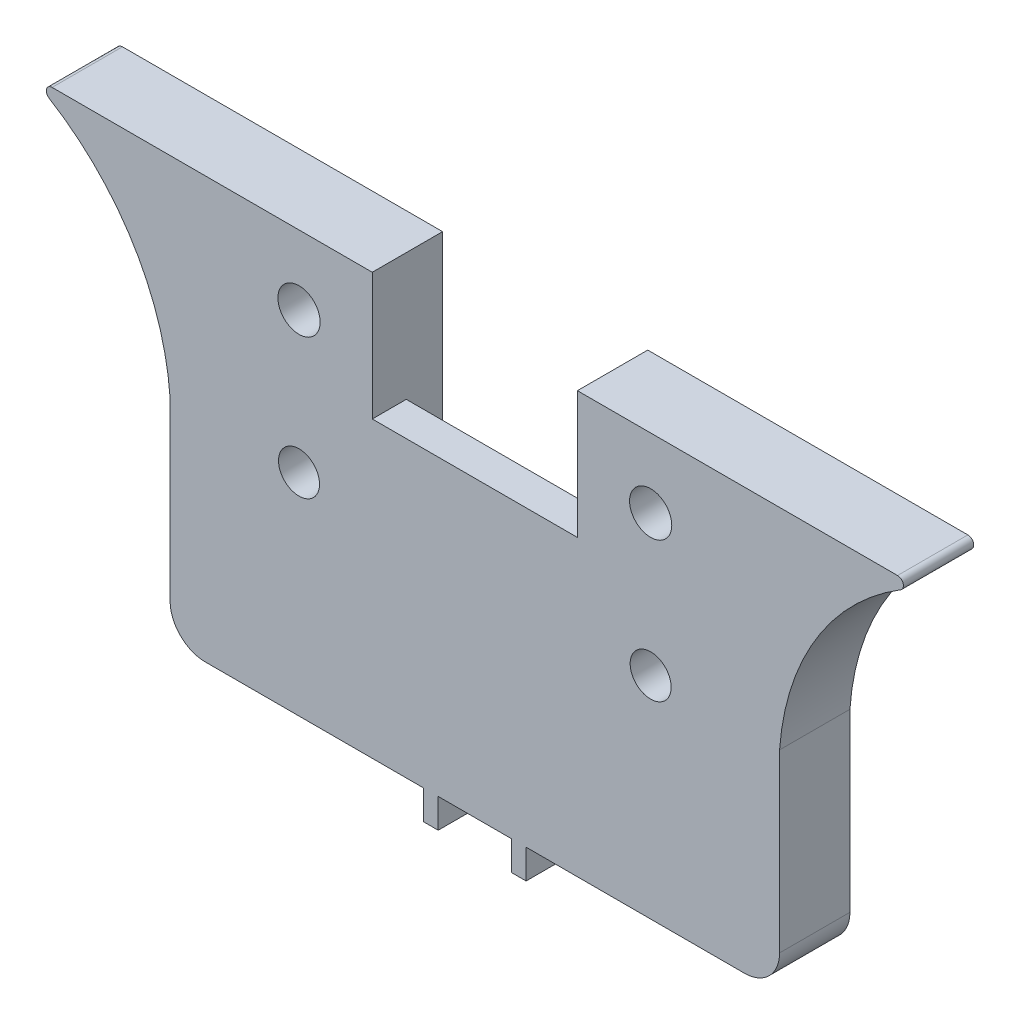
SolidWorks part; units mm, degrees
ref_plane "Front Plane" through (0, 0, 0) normal (0, 0, 1) x (1, 0, 0)
ref_plane "Top Plane" through (0, 0, 0) normal (0, 1, 0) x (1, 0, 0)
ref_plane "Right Plane" through (0, 0, 0) normal (1, 0, 0) x (0, 0, -1)
sketch "Sketch2" plane through (0, 0, 0) normal (0, 0, 1) x (1, 0, 0)
  line L0 (0, -33.2846) -> (0, 67.9981) construction
  line L12 (45.8007, 37.8996) -> (-45.8007, 37.8996)
  line L13 (-33.02, 15.1445) -> (-33.02, -3.9055)
  line L14 (-29.21, -7.7155) -> (29.21, -7.7155)
  line L15 (33.02, 15.1445) -> (33.02, -3.9055)
  circle A4 centre (-19.05, 15.1445) radius 2.2225
  circle A12 centre (19.05, 15.1445) radius 2.2225
  arc A13 (-33.02, 15.1445) -> (-46.1321, 36.723) centre (-60.5269, 13.203) ccw
  arc A14 (33.02, 15.1445) -> (46.1321, 36.723) centre (60.5269, 13.203) cw
  arc A15 (33.02, -3.9055) -> (29.21, -7.7155) centre (29.21, -3.9055) cw
  arc A16 (-33.02, -3.9055) -> (-29.21, -7.7155) centre (-29.21, -3.9055) ccw
  arc A17 (46.1321, 36.723) -> (45.8007, 37.8996) centre (45.8007, 37.2646) ccw
  arc A18 (-45.8007, 37.8996) -> (-46.1321, 36.723) centre (-45.8007, 37.2646) ccw
  point P4 (0, 57.6776)
  point P9 (0, 19.5776)
  point P12 (0, 37.8996)
  point P16 (0, -7.7155)
  point P18 (33.02, -7.7155)
  point P20 (0, -3.9055)
  point P22 (-33.02, -7.7155)
  point P27 (48.26, 37.8996)
  point P30 (-48.26, 37.8996)
  dimension "D2" = 48.26
  dimension "D3" = 22.86
  dimension "D6" = 0.635
  dimension "D4" = 33.02
  dimension "D5" = 3.81
  dimension "D7" = 27.5753
  dimension "D8" = 19.05
  dimension "D9" = 45.8007
  dimension "D10" = 19.05
  dimension "D11" = 19.5776
  dimension "D12" = 57.6776
  dimension "D1" = 4.445
extrude "Boss-Extrude1" add sketch "Sketch2" along normal blind 7.62
sketch "Sketch11" plane through (0, 0, 7.62) normal (0, 0, 1) x (1, 0, 0)
  line L0 (0, 41.9648) -> (0, -47.1588) construction
  line L1 (-19.05, 15.1445) -> (-19.05, 30.3845) construction
  circle A0 centre (-19.05, 30.3845) radius 2.286
  circle A1 centre (19.05, 30.3845) radius 2.286
  dimension "D2" = 4.572
  dimension "D1" = 15.24
extrude "Cut-Extrude9" cut sketch "Sketch11" against normal through all
sketch "Sketch12" plane through (0, 0, 0) normal (0, 0, 1) x (1, 0, 0)
  line L0 (0, 39.594) -> (0, -43.4023) construction
  line L1 (-4.7625, 33.4498) -> (4.7625, 33.4498)
  line L3 (4.7625, 10.9708) -> (-4.7625, 10.9708)
  line L4 (-11.1125, 17.3208) -> (-11.1125, 27.0998)
  line L5 (11.1125, 17.3208) -> (11.1125, 27.0998)
  arc A0 (11.1125, 27.0998) -> (4.7625, 33.4498) centre (4.7625, 27.0998) ccw
  arc A1 (11.1125, 17.3208) -> (4.7625, 10.9708) centre (4.7625, 17.3208) cw
  arc A2 (-4.7625, 10.9708) -> (-11.1125, 17.3208) centre (-4.7625, 17.3208) cw
  arc A3 (-4.7625, 33.4498) -> (-11.1125, 27.0998) centre (-4.7625, 27.0998) ccw
  point P10 (0, 10.9708)
  point P11 (0, 33.4498)
  point P13 (11.1125, 33.4498)
  point P16 (11.1125, 10.9708)
  point P19 (-11.1125, 10.9708)
  point P22 (-11.1125, 33.4498)
  dimension "D4" = 6.35
  dimension "D1" = 11.1125
  dimension "D2" = 10.9708
  dimension "D3" = 22.479
extrude "Cut-Extrude11" cut sketch "Sketch12" along normal blind 3.937
sketch "Sketch13" plane through (0, 0, 0) normal (0, 0, -1) x (-1, 0, 0)
  line L2 (-11.1125, 40.3062) -> (-11.1125, 24.1288)
  line L3 (-11.1125, 24.1288) -> (11.1125, 24.1288)
  line L7 (-11.1125, 40.3062) -> (11.1125, 40.3062)
  line L8 (11.1125, 40.3062) -> (11.1125, 24.1288)
  dimension "D1" = 11.1125
  dimension "D2" = 11.1125
  dimension "D3" = 24.1288
  dimension "D4" = 40.3062
extrude "Cut-Extrude12" cut sketch "Sketch13" against normal through all
sketch "Sketch15" plane through (0, -7.7155, 0) normal (0, -1, 0) x (1, 0, 0)
  line L0 (0, -11.1019) -> (0, 17.7532) construction
  line L1 (-29.21, 3.81) -> (29.21, 3.81) construction
  line L4 (-29.21, 7.62) -> (-29.21, 0) construction
  line L5 (29.21, 7.62) -> (29.21, 0) construction
  circle A0 centre (0, 3.81) radius 2.032
  dimension "D1" = 4.064
extrude "Cut-Extrude14" cut sketch "Sketch15" against normal blind 17.78
sketch "Sketch16" plane through (0, 0, 0) normal (0, 0, -1) x (-1, 0, 0)
  line L0 (29.21, -7.7155) -> (-29.21, -7.7155) construction
  line L1 (-3.9687, -7.7155) -> (-5.5563, -7.7155)
  line L2 (-3.9687, -7.7155) -> (-3.9688, -10.8905)
  line L3 (-3.9688, -10.8905) -> (-5.5563, -10.8905)
  line L4 (-5.5563, -7.7155) -> (-5.5563, -10.8905)
  line L5 (0, -11.3212) -> (0, 10.1435) construction
  line L6 (5.5562, -7.7155) -> (3.9688, -7.7155)
  line L7 (5.5562, -7.7155) -> (5.5562, -10.8905)
  line L8 (5.5562, -10.8905) -> (3.9688, -10.8905)
  line L9 (3.9688, -7.7155) -> (3.9688, -10.8905)
  dimension "D1" = 1.5875
  dimension "D2" = 3.175
  dimension "D3" = 7.9375
  dimension "D4" = 3.9688
extrude "Boss-Extrude2" add sketch "Sketch16" against normal up to surface (7.62 mm away) up to face at (-16.764, 30.3845, 7.62)
equation "\"D4@Sketch16\"=\"D3@Sketch16\"/2"
